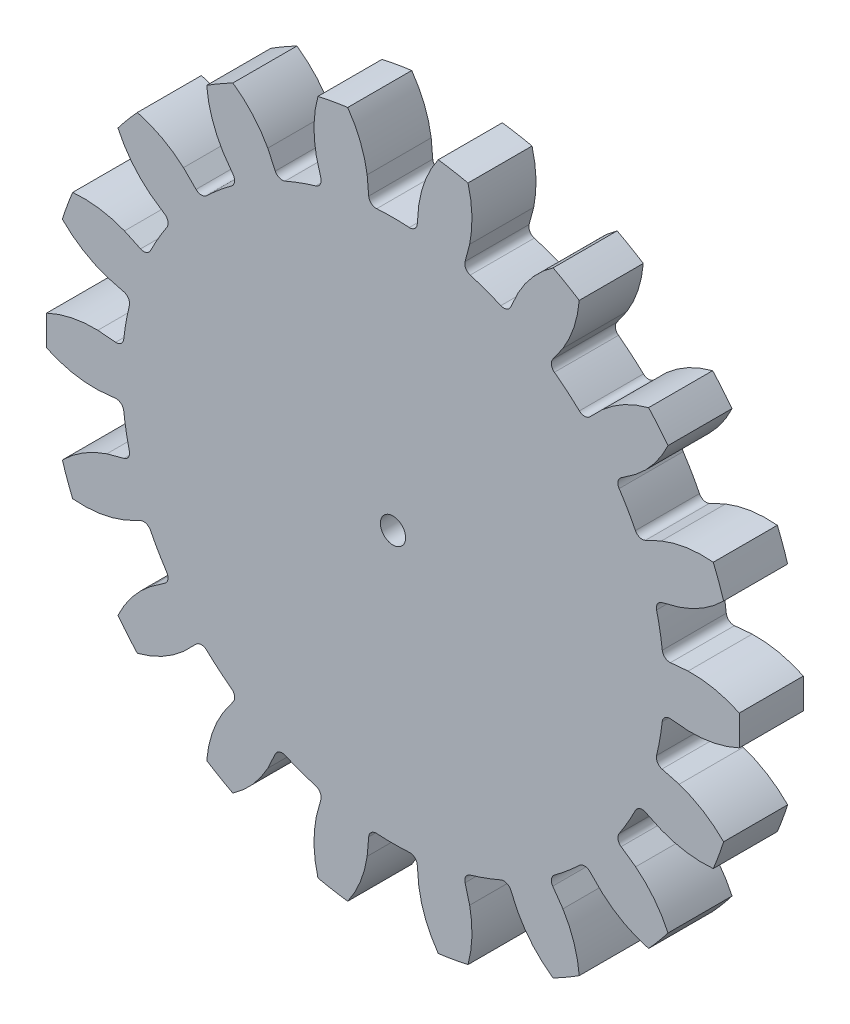
SolidWorks part; units mm, degrees
ref_plane "Front Plane" through (0, 0, 0) normal (0, 0, 1) x (1, 0, 0)
ref_plane "Top Plane" through (0, 0, 0) normal (0, 1, 0) x (1, 0, 0)
ref_plane "Right Plane" through (0, 0, 0) normal (1, 0, 0) x (0, 0, -1)
sketch "Sketch1" plane through (0, 0, 0) normal (0, 0, 1) x (1, 0, 0)
  line L0 (0, 0) -> (137.5, 0) construction
  line L1 (0, 0) -> (105.8668, 18.6672) construction
  line L2 (0, 0) -> (136.9768, 11.9839) construction
  line L3 (0, 0) -> (117.3882, 5.1253) construction
  line L4 (117.0529, 10.2408) -> (107.0909, 9.3692)
  line L5 (105.8668, 18.6672) -> (0, 0)
  line L6 (117.0529, -10.2408) -> (107.0909, -9.3692)
  line L7 (105.8668, -18.6672) -> (0, 0)
  circle A0 centre (0, 0) radius 137.5 construction
  circle A1 centre (0, 0) radius 117.5 construction
  circle A2 centre (0, 0) radius 107.5 construction
  arc A3 (117.0529, 10.2408) -> (137.3694, 5.992) centre (118.3599, -34.2074) cw
  arc A4 (105.8668, 18.6672) -> (107.0909, 9.3692) centre (0, 0) cw
  arc A5 (137.3694, 5.992) -> (137.5, 0) centre (0, 0) cw
  arc A6 (137.3694, -5.992) -> (137.5, 0) centre (0, 0) ccw
  arc A7 (117.0529, -10.2408) -> (137.3694, -5.992) centre (118.3599, 34.2074) ccw
  arc A8 (105.8668, -18.6672) -> (107.0909, -9.3692) centre (0, 0) ccw
  dimension "D1" = 275
  dimension "D2" = 20
  dimension "D3" = 30
  dimension "D7" = 215
  dimension "D4" = 10
  dimension "D5" = 5
  dimension "D6" = 2.5
extrude "Boss-Extrude1" add sketch "Sketch1" along normal blind 25.4 contours L7 A8 L6 A7 A6 A5 A3 L4 A4 L5 region at (82.1577, 0, 0)
fillet "Fillet1" radius 3 2 edges at (107.0909, 9.3692, 12.7) (107.0909, -9.3692, 12.7)
pattern_circular "CirPattern1" count 18 over 360 about axis through (0, 0, 25.4) along (0, 0, -1) of "Fillet1", "Boss-Extrude1"
sketch "Sketch2" plane through (0, 0, 0) normal (0, 0, -1) x (-1, 0, 0)
  circle A0 centre (0, 0) radius 5
  dimension "D1" = 10
extrude "Cut-Extrude1" cut sketch "Sketch2" against normal up to next
